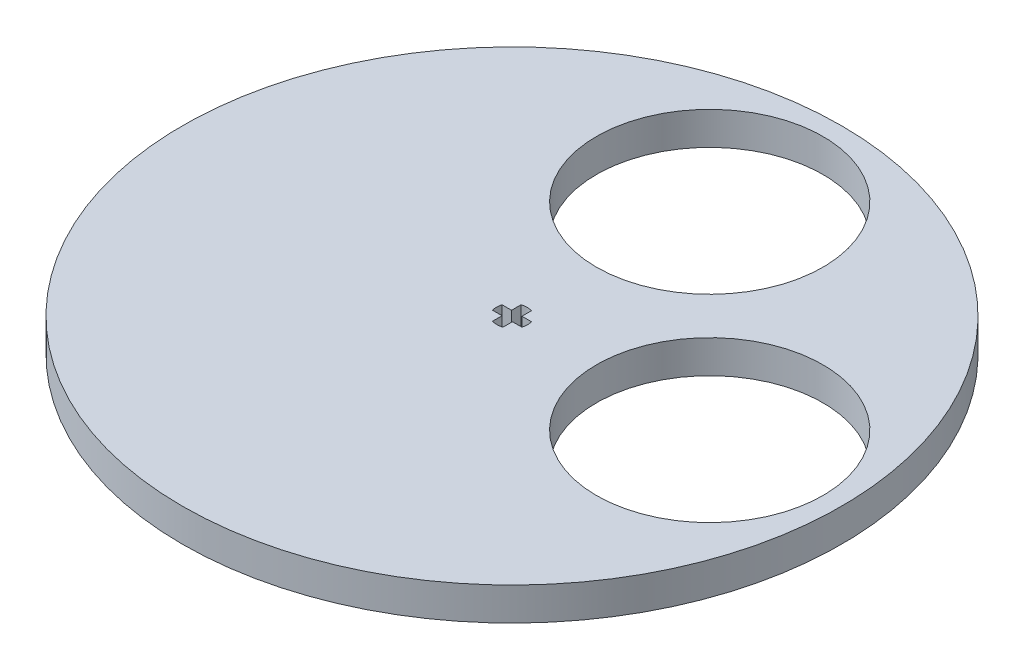
SolidWorks part; units mm, degrees
ref_plane "Front Plane" through (0, 0, 0) normal (0, 0, 1) x (1, 0, 0)
ref_plane "Top Plane" through (0, 0, 0) normal (0, 1, 0) x (1, 0, 0)
ref_plane "Right Plane" through (0, 0, 0) normal (1, 0, 0) x (0, 0, -1)
sketch "Sketch6" plane through (0, 0, 0) normal (0, 1, 0) x (1, 0, 0)
  circle A2 centre (63.5, 63.5) radius 50.8
  dimension "D1" = 101.6
extrude "Boss-Extrude3" add sketch "Sketch6" along normal blind 5.08 contours A2
sketch "Sketch11" plane through (0, 5.08, 0) normal (0, 1, 0) x (1, 0, 0)
  line L0 (63.5, 114.3) -> (63.5, 63.5)
  line L1 (63.5, 63.5) -> (114.3, 63.5)
  circle A0 centre (63.5, 93.98) radius 17.4625
  circle A1 centre (93.98, 63.5) radius 17.4625
  circle A2 centre (63.5, 63.5) radius 50.8 construction
  dimension "D1" = 34.925
  dimension "D2" = 20.32
  dimension "D3" = 20.32
extrude "Cut-Extrude2" cut sketch "Sketch11" against normal through all contours L0 A0 | L0 A0 | L1 A1 | L1 A1 | A0 region at (70.9113, 5.08, -93.98) region at (93.98, 5.08, -70.9113) region at (93.98, 5.08, -56.0887) region at (56.0887, 5.08, -93.98)
sketch "Sketch12" plane through (0, 5.08, 0) normal (0, 1, 0) x (1, 0, 0)
  line L0 (62.7, 64.2314) -> (62.7, 65.6941)
  line L1 (64.3, 65.6941) -> (64.3, 64.2314)
  line L2 (62.7, 64.2314) -> (64.3, 64.2314) construction
  line L3 (62.7, 64.2314) -> (62.7, 62.7686) construction
  line L4 (62.7, 64.2314) -> (61.2373, 64.2314)
  line L5 (61.2373, 62.7686) -> (62.7, 62.7686)
  line L6 (62.7, 62.7686) -> (62.7, 61.3059)
  line L7 (64.3, 61.3059) -> (64.3, 62.7686)
  line L8 (64.3, 62.7686) -> (65.7627, 62.7686)
  line L9 (64.3, 64.2314) -> (65.7627, 64.2314)
  circle A0 centre (63.5, 63.5) radius 2.75
  circle A1 centre (63.5, 63.5) radius 2.5157 construction
  arc A2 (62.7, 65.6941) -> (64.3, 65.6941) centre (63.5, 63.2202) cw
  arc A3 (61.2373, 64.2314) -> (61.2373, 62.7686) centre (63.7323, 63.5) ccw
  arc A4 (62.7, 61.3059) -> (64.3, 61.3059) centre (63.5, 63.7798) ccw
  arc A5 (65.7627, 64.2314) -> (65.7627, 62.7686) centre (63.2677, 63.5) cw
  point P9 (63.5, 64.2314)
  point P23 (61.1323, 63.5)
  point P24 (63.5, 61.1798)
  point P25 (173.3338, 39.6483)
  point P26 (163.4864, 41.8855)
  point P27 (158.1368, 42.5294)
  point P28 (138.6628, 46.6853)
  point P29 (126.7567, 50.0863)
  point P30 (94.9276, 62.7693)
  point P31 (82.3827, 62.8404)
  point P32 (70.4652, 64.8428)
  point P33 (0, 0)
  point P34 (84.1171, 62.7686)
  dimension "D1" = 5.5
  dimension "D4" = 2.6
  dimension "D5" = 5.0313
  dimension "D2" = 1.4627
  dimension "D3" = 1.6
extrude "Cut-Extrude3" cut sketch "Sketch12" against normal through all contours A0
extrude "Boss-Extrude4" add sketch "Sketch12<3>" against normal up to surface (5.08 mm away) up to face at (63.5, 0, -60.75)
sketch "Sketch12<3>" plane through (0, 5.08, 0) normal (0, 1, 0) x (1, 0, 0) same geometry as "Sketch12"
